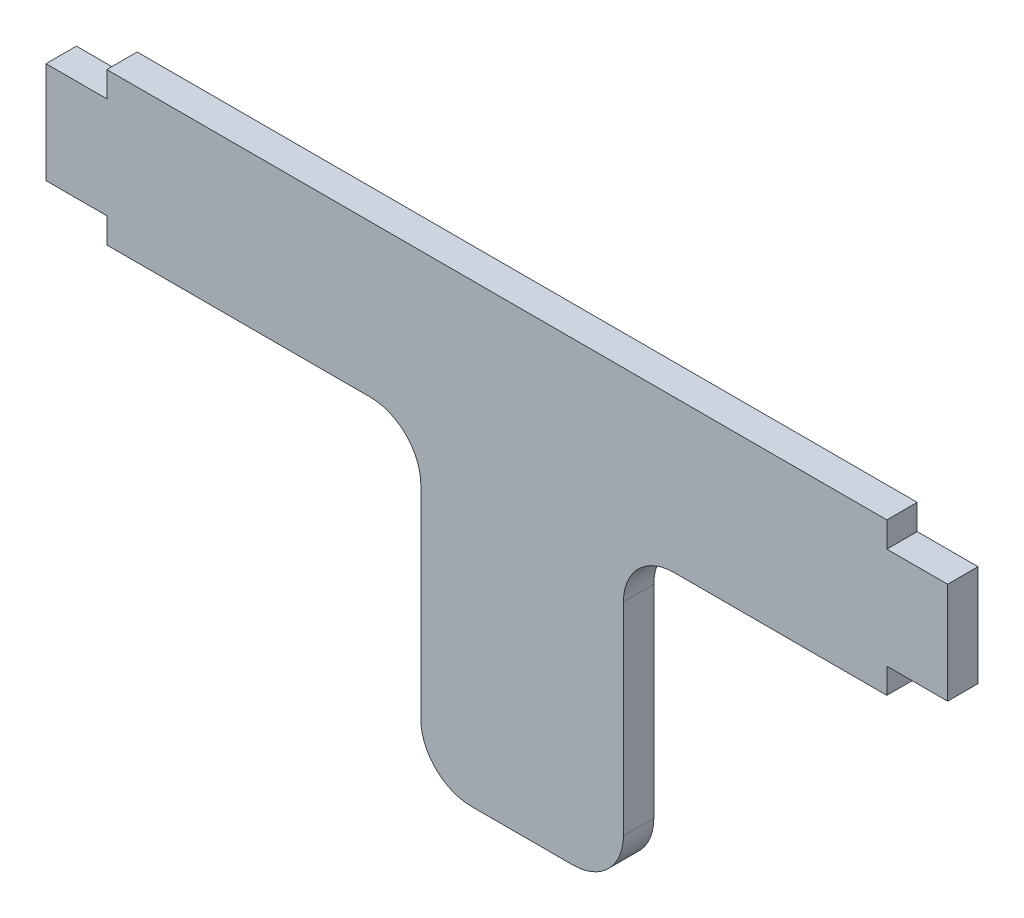
SolidWorks part; units mm, degrees
material "MDF"
ref_plane "Plano frontal" through (0, 0, 0) normal (0, 0, 1) x (1, 0, 0)
ref_plane "Plano superior" through (0, 0, 0) normal (0, 1, 0) x (1, 0, 0)
ref_plane "Plano direito" through (0, 0, 0) normal (1, 0, 0) x (0, 0, -1)
sketch "Esboço1" plane through (0, 0, 0) normal (0, 0, 1) x (1, 0, 0)
  line L0 (0, 0) -> (0, 7.5) construction
  line L1 (38.5, -7.5) -> (-38.5, -7.5)
  line L2 (38.5, -7.5) -> (38.5, 7.5)
  line L3 (38.5, 7.5) -> (-38.5, 7.5)
  line L4 (-38.5, -7.5) -> (-38.5, 7.5)
  line L5 (38.5, -7.5) -> (-38.5, 7.5) construction
  line L6 (38.5, 7.5) -> (-38.5, -7.5) construction
  line L7 (12.5, -37.5) -> (-7.5, -37.5)
  line L8 (12.5, -37.5) -> (12.5, -7.5)
  line L9 (12.5, -7.5) -> (-7.5, -7.5)
  line L10 (-7.5, -37.5) -> (-7.5, -7.5)
  line L11 (12.5, -37.5) -> (-7.5, -7.5) construction
  line L12 (12.5, -7.5) -> (-7.5, -37.5) construction
  line L13 (-44.5, -5) -> (-38.5, -5)
  line L14 (-44.5, -5) -> (-44.5, 5)
  line L15 (-44.5, 5) -> (-38.5, 5)
  line L16 (-38.5, -5) -> (-38.5, 5)
  line L17 (-44.5, -5) -> (-38.5, 5) construction
  line L18 (-44.5, 5) -> (-38.5, -5) construction
  line L19 (44.5, 5) -> (38.5, 5)
  line L20 (38.5, -5) -> (38.5, 5)
  line L21 (44.5, -5) -> (38.5, -5)
  line L22 (44.5, -5) -> (44.5, 5)
  point P0 (0, 0)
  point P6 (2.5, -22.5)
  point P12 (-41.5, 0)
  dimension "D1" = 77
  dimension "D2" = 30
  dimension "D3" = 15
  dimension "D4" = 20
  dimension "D5" = 6
  dimension "D6" = 10
  dimension "D7" = 42
extrude "Ressalto-extrusão1" add sketch "Esboço1" along normal blind 3 contours L4 L1 L2 L3 | L10 L7 L8 L1 | L21 L22 L19 L2 | L15 L14 L13 L4 region at (0, 0, 0) region at (2.5, -22.5, 0) region at (41.5, 0, 0) region at (-41.5, 0, 0)
fillet "Filete1" radius 5 4 edges at (12.5, -37.5, 1.5) (-7.5, -37.5, 1.5) (-7.5, -7.5, 1.5) (12.5, -7.5, 1.5)
